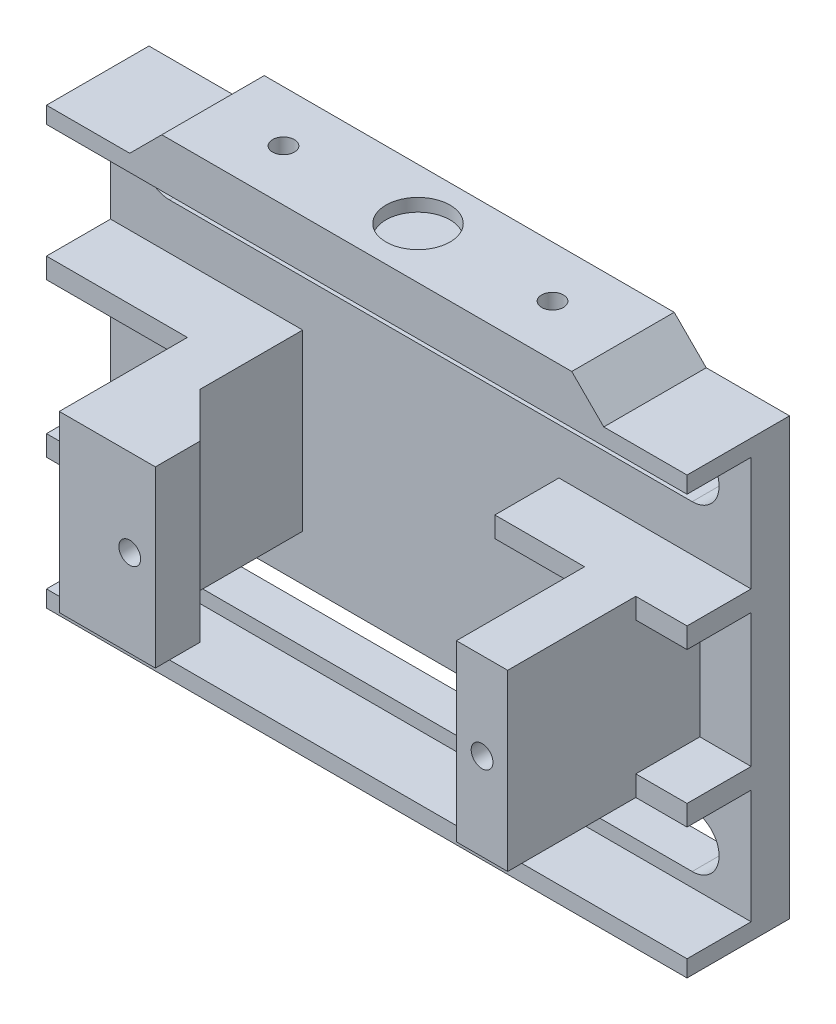
SolidWorks part; units mm, degrees
ref_plane "Płaszczyzna przednia" through (0, 0, 0) normal (0, 0, 1) x (1, 0, 0)
ref_plane "Płaszczyzna górna" through (0, 0, 0) normal (0, 1, 0) x (1, 0, 0)
ref_plane "Płaszczyzna prawa" through (0, 0, 0) normal (1, 0, 0) x (0, 0, -1)
sketch "Szkic1" plane through (0, 0, 0) normal (0, 0, 1) x (1, 0, 0)
  line L1 (25, 17) -> (-25, 17)
  line L2 (25, 17) -> (25, -17)
  line L3 (25, -17) -> (-25, -17)
  line L4 (-25, 17) -> (-25, -17)
  line L5 (25, 17) -> (-25, -17) construction
  line L6 (25, -17) -> (-25, 17) construction
  point P0 (0, 0)
  dimension "D1" = 50
  dimension "D2" = 34
extrude "Dodanie-wyciągnięcie1" add sketch "Szkic1" along normal blind 3
sketch "Szkic3" plane through (0, 0, 0) normal (0, 0, 1) x (1, 0, 0)
  line L0 (-25, 12.5) -> (25, 12.5) construction
  line L1 (25, -17) -> (25, 17) construction
  line L2 (-25, 17) -> (-25, -17) construction
  line L3 (25, 17) -> (-25, 17) construction
  line L4 (-20.4, 14.6) -> (20.4, 14.6)
  line L5 (-20.4, 10.4) -> (20.4, 10.4)
  line L6 (25, -17) -> (25, 17) construction
  line L7 (-25, 17) -> (-25, -17) construction
  arc A0 (-20.4, 14.6) -> (-20.4, 10.4) centre (-20.4, 12.5) ccw
  arc A1 (20.4, 14.6) -> (20.4, 10.4) centre (20.4, 12.5) cw
  dimension "D1" = 4.5
  dimension "D2" = 4.2
  dimension "D3" = 2.5
  dimension "D4" = 2.5
extrude "Wytnij-wyciągnięcie1" cut sketch "Szkic3" along normal through all
sketch "Szkic2" plane through (0, 0, 3) normal (0, 0, 1) x (1, 0, 0)
  line L4 (-25, 17) -> (-25, -17)
  line L5 (-25, -17) -> (25, -17)
  line L6 (25, -17) -> (25, 17)
  line L7 (25, 17) -> (-25, 17)
  line L8 (-25, 17) -> (-25, 15.7)
  line L11 (25, 17) -> (-25, 17)
  line L12 (25, 15.7) -> (-25, 15.7)
  line L14 (25, 15.7) -> (25, 17)
  line L16 (-25, 6.8) -> (-10, 6.8)
  line L17 (-25, 17) -> (-25, -17) construction
  line L18 (-10, 6.8) -> (-10, 5.2)
  line L19 (-10, 5.2) -> (-25, 5.2)
  line L20 (-25, 5.2) -> (-25, 6.8)
  line L21 (0, 0) -> (0, 17) construction
  line L22 (25, 5.2) -> (25, 6.8)
  line L23 (10, 5.2) -> (25, 5.2)
  line L24 (10, 6.8) -> (10, 5.2)
  line L25 (25, 6.8) -> (10, 6.8)
  dimension "D3" = 8.9
  dimension "D4" = 1.6
  dimension "D5" = 10
  dimension "D1" = 0
  dimension "D2" = 1.3
extrude "Dodanie-wyciągnięcie2" add sketch "Szkic2" along normal blind 5
mirror "Lustro1" about plane through (0, 0, 0) normal (0, 1, 0) of "Wytnij-wyciągnięcie1", "Dodanie-wyciągnięcie2"
sketch "Szkic8" plane through (0, 0, 0) normal (0, 0, -1) x (-1, 0, 0)
  line L0 (-18.5, 17) -> (-16, 19.5)
  line L1 (-25, 17) -> (25, 17) construction
  line L2 (-16, 19.5) -> (16, 19.5)
  line L3 (16, 19.5) -> (18.5, 17)
  line L4 (-18.5, 17) -> (18.5, 17)
  point P4 (0, 19.5)
  point P7 (0, 17)
  dimension "D1" = 2.5
  dimension "D2" = 2.5
  dimension "D3" = 32
extrude "Dodanie-wyciągnięcie5" add sketch "Szkic8" against normal up to surface (8 mm away) up to face at (0, 16.35, 8)
sketch "Szkic9" plane through (0, 19.5, 0) normal (0, 1, 0) x (1, 0, 0)
  line L0 (-16, -8) -> (-16, 0) construction
  line L1 (0, 0) -> (0, -8) construction
  line L2 (-16, 0) -> (16, 0) construction
  line L3 (-16, -8) -> (16, -8) construction
  circle A0 centre (10.5, -4) radius 0.85
  circle A1 centre (-10.5, -4) radius 0.85
  circle A2 centre (0, -4) radius 2.5
  point P7 (-16, -4)
  dimension "D1" = 21
  dimension "D2" = 1.7
  dimension "D3" = 5
extrude "Wytnij-wyciągnięcie3" cut sketch "Szkic9" against normal blind 3 contours A1 | A0 region at (10.5, 19.5, 4) region at (-10.5, 19.5, 4)
extrude "Wytnij-wyciągnięcie4" cut sketch "Szkic9<3>" against normal blind 1 contours A2 L1 | L1 A2 region at (1.061, 19.5, 4) region at (-1.061, 19.5, 4)
sketch "Szkic9<3>" plane through (0, 19.5, 0) normal (0, 1, 0) x (1, 0, 0) same geometry as "Szkic9"
sketch "Szkic5" plane through (0, 0, 3) normal (0, 0, 1) x (1, 0, 0)
  line L0 (25, 6.8) -> (10, 6.8) construction
  line L1 (17, 6.8) -> (21, 6.8)
  line L2 (17, 6.8) -> (17, -6.8)
  line L3 (17, -6.8) -> (21, -6.8)
  line L4 (21, 6.8) -> (21, -6.8)
  line L5 (25, -6.8) -> (10, -6.8) construction
  line L6 (25, -5.2) -> (25, 5.2) construction
  line L7 (-10, 6.8) -> (-25, 6.8) construction
  line L8 (-10, 6.8) -> (-14, 6.8)
  line L9 (-10, 6.8) -> (-10, -6.8)
  line L10 (-10, -6.8) -> (-14, -6.8)
  line L11 (-14, 6.8) -> (-14, -6.8)
  line L12 (-10, -6.8) -> (-25, -6.8) construction
  dimension "D1" = 8
  dimension "D2" = 4
  dimension "D3" = 10
  dimension "D4" = 4
extrude "Dodanie-wyciągnięcie3" add sketch "Szkic5" along normal blind 15
sketch "Szkic6" plane through (0, 0, 0) normal (0, 1, 0) x (1, 0, 0)
  line L0 (-10, -18) -> (-6.5, -18)
  line L2 (-10, -11) -> (-10, -18)
  line L3 (-10, -18) -> (-10, -3) construction
  line L4 (-10, -18) -> (-14, -18) construction
  line L5 (-6.5, -18) -> (-6.5, -14.5)
  line L6 (-6.5, -14.5) -> (-10, -11)
  dimension "D1" = 3.5
  dimension "D2" = 3.5
  dimension "D3" = 45
extrude "Dodanie-wyciągnięcie4" add sketch "Szkic6" along normal up to surface (6.8 mm away) and the other way up to surface (6.8 mm away) up to face at (-16.3333, 6.8, 9.6667) other way up to face at (-16.3333, -6.8, 9.6667)
sketch "Szkic7" plane through (0, 0, 18) normal (0, 0, 1) x (1, 0, 0)
  line L0 (-8.5, 0) -> (19, 0) construction
  line L1 (0, -17) -> (0, 17) construction
  line L2 (25, 17) -> (18.5, 17) construction
  circle A0 centre (-8.5, 0) radius 0.85
  circle A1 centre (19, 0) radius 0.85
  point P11 (0, 0)
  dimension "D3" = 1.7
  dimension "D1" = 8.5
  dimension "D2" = 19
extrude "Wytnij-wyciągnięcie2" cut sketch "Szkic7" against normal blind 8
